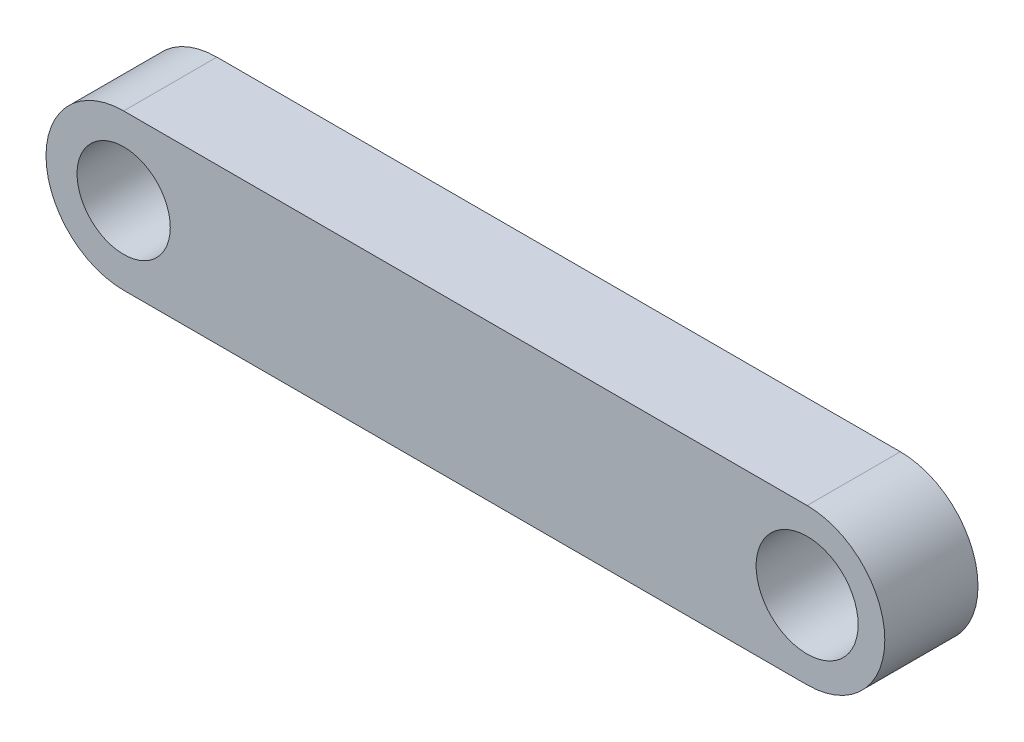
SolidWorks part; units mm, degrees
ref_plane "Front Plane" through (0, 0, 0) normal (0, 0, 1) x (1, 0, 0)
ref_plane "Top Plane" through (0, 0, 0) normal (0, 1, 0) x (1, 0, 0)
ref_plane "Right Plane" through (0, 0, 0) normal (1, 0, 0) x (0, 0, -1)
sketch "Sketch1" plane through (0, 0, 0) normal (0, 0, 1) x (1, 0, 0)
  line L0 (0, 0) -> (22, 0) construction
  line L1 (0, 2.5) -> (22, 2.5)
  line L2 (22, -2.5) -> (0, -2.5)
  circle A0 centre (0, 0) radius 1.5
  circle A1 centre (22, 0) radius 1.6417
  arc A2 (0, 2.5) -> (0, -2.5) centre (0, 0) ccw
  arc A3 (22, -2.5) -> (22, 2.5) centre (22, 0) ccw
  dimension "D1" = 3
  dimension "D2" = 3.2833
  dimension "D3" = 5
  dimension "D4" = 5
  dimension "D5" = 22
extrude "Boss-Extrude1" add sketch "Sketch1" along normal blind 3
